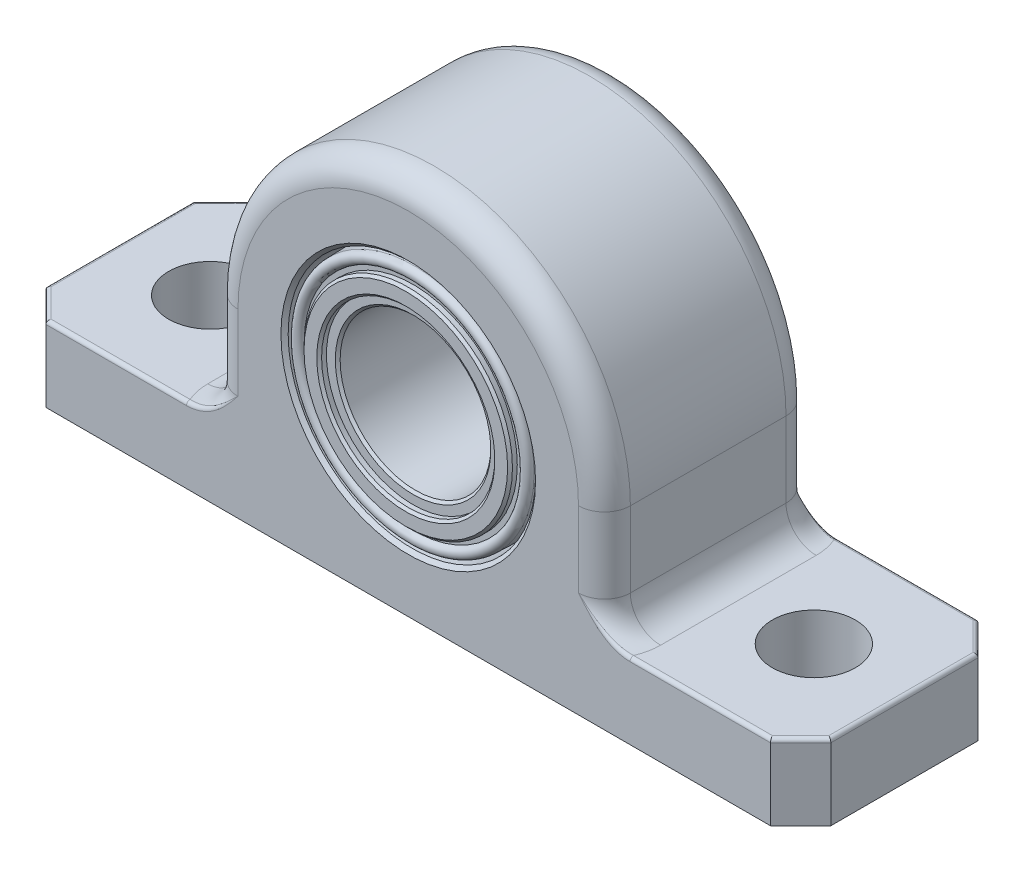
SolidWorks part; units mm, degrees
ref_plane "Front Plane" through (0, 0, 0) normal (0, 0, 1) x (1, 0, 0)
ref_plane "Top Plane" through (0, 0, 0) normal (0, 1, 0) x (1, 0, 0)
ref_plane "Right Plane" through (0, 0, 0) normal (1, 0, 0) x (0, 0, -1)
sketch "Sketch1" plane through (0, 0, 0) normal (0, 0, 1) x (1, 0, 0)
  line L0 (-41.275, 0) -> (41.275, 0)
  line L1 (41.275, 0) -> (41.275, 7.9375)
  line L2 (-41.275, 0) -> (-41.275, 7.9375)
  line L3 (-41.275, 7.9375) -> (-20.6375, 7.9375)
  line L4 (41.275, 7.9375) -> (20.6375, 7.9375)
  line L5 (-20.6375, 7.9375) -> (-20.6375, 19.05)
  line L6 (20.6375, 7.9375) -> (20.6375, 19.05)
  line L7 (0, 0) -> (0, 39.6875) construction
  line L8 (5.6037, 24.6537) -> (14.5929, 33.6429) construction
  circle A0 centre (0, 19.05) radius 7.9248
  arc A1 (20.6375, 19.05) -> (-20.6375, 19.05) centre (0, 19.05) ccw
  circle A2 centre (0, 19.05) radius 13.0099 construction
  point P16 (9.1994, 28.2494)
  point P17 (0, 26.9748)
  point P18 (0, 32.0599)
  dimension "ID" = 15.8496
  dimension "Overall Height" = 39.6875
  dimension "Overall Length" = 82.55
  dimension "CAD B" = 7.9375
  dimension "Center Height" = 19.05
  dimension "D1" = 45
  dimension "D2" = 12.7127
  dimension "D3" = 5.0851
sketch "Sketch2" plane through (0, 0, 0) normal (0, 1, 0) x (1, 0, 0)
  line L0 (-31.75, 0) -> (31.75, 0) construction
  line L1 (-41.275, -10.9141) -> (41.275, 10.9141) construction
  line L2 (-41.275, 10.9141) -> (41.275, 10.9141)
  line L3 (-41.275, 10.9141) -> (-41.275, -10.9141)
  line L4 (-41.275, -10.9141) -> (41.275, -10.9141)
  line L5 (41.275, 10.9141) -> (41.275, -10.9141)
  circle A0 centre (-31.75, 0) radius 4.3656
  circle A1 centre (31.75, 0) radius 4.3656
  dimension "Mounting Hole" = 8.7312
  dimension "Mounting Center" = 63.5
  dimension "Overall Width" = 21.8281
sketch "Sketch3" plane through (0, 0, 0) normal (0, 0, 1) x (1, 0, 0)
  line L0 (-41.275, 0) -> (-41.275, 7.9375) construction
  line L1 (-41.275, 0) -> (41.275, 0) construction
  line L2 (-41.275, 7.9375) -> (-20.6375, 7.9375) construction
  line L3 (41.275, 7.9375) -> (20.6375, 7.9375) construction
  line L4 (41.275, 0) -> (41.275, 7.9375) construction
  line L5 (20.6375, 7.9375) -> (20.6375, 19.05) construction
  line L6 (-20.6375, 7.9375) -> (-20.6375, 19.05) construction
  line L7 (-41.275, 0) -> (-41.275, 7.9375)
  line L8 (-41.275, 0) -> (41.275, 0)
  line L9 (-41.275, 7.9375) -> (-20.6375, 7.9375)
  line L10 (41.275, 7.9375) -> (20.6375, 7.9375)
  line L11 (41.275, 0) -> (41.275, 7.9375)
  line L12 (20.6375, 7.9375) -> (20.6375, 19.05)
  line L13 (-20.6375, 7.9375) -> (-20.6375, 19.05)
  arc A0 (20.6375, 19.05) -> (-20.6375, 19.05) centre (0, 19.05) ccw construction
  circle A1 centre (0, 19.05) radius 13.0099 construction
  arc A2 (20.6375, 19.05) -> (-20.6375, 19.05) centre (0, 19.05) ccw
  circle A3 centre (0, 19.05) radius 13.0099
extrude "Boss-Extrude1" add sketch "Sketch3" against normal up to vertex (10.9141 mm away) and the other way up to vertex (10.9141 mm away) up to point (-41.275, 0, -10.9141) other way up to point (-41.275, 0, 10.9141)
sketch "Sketch4" plane through (0, 0, 0) normal (0, 1, 0) x (1, 0, 0)
  circle A0 centre (-31.75, 0) radius 4.3656 construction
  circle A1 centre (31.75, 0) radius 4.3656 construction
  circle A2 centre (-31.75, 0) radius 4.3656
  circle A3 centre (31.75, 0) radius 4.3656
extrude "Cut-Extrude1" cut sketch "Sketch4" along normal through all
chamfer "Chamfer1" distance 3.175 angle 45 4 edges at (-41.275, 3.9688, -10.9141) (41.275, 3.9688, 10.9141) (41.275, 3.9688, -10.9141) (-41.275, 3.9688, 10.9141)
fillet "Fillet1" radius 2.7285 6 edges at (-20.6375, 13.4938, -10.9141) (0, 39.6875, -10.9141) (-20.6375, 13.4938, 10.9141) (0, 39.6875, 10.9141) (20.6375, 13.4938, -10.9141) (20.6375, 13.4938, 10.9141)
fillet "Fillet2" radius 3.175 6 edges at (-19.8383, 7.9375, -10.1149) (-19.8383, 7.9375, 10.1149) (19.8383, 7.9375, -10.1149) (19.8383, 7.9375, 10.1149) (-20.6375, 7.9375, 0) (20.6375, 7.9375, 0)
chamfer "Chamfer2" distance 0.381 angle 45 2 edges at (13.0099, 19.05, 10.9141) (13.0099, 19.05, -10.9141)
fillet "Fillet3" radius 0.381 14 edges at (-21.6682, 8.1975, -10.9141) (-21.6682, 8.1975, 10.9141) (21.6682, 8.1975, -10.9141) (21.6682, 8.1975, 10.9141) (-30.6221, 7.9375, -10.9141) (-39.6875, 7.9375, -9.3266) (-41.275, 7.9375, 0) (-39.6875, 7.9375, 9.3266) (-30.6221, 7.9375, 10.9141) (30.6221, 7.9375, -10.9141) (39.6875, 7.9375, -9.3266) (41.275, 7.9375, 0) (39.6875, 7.9375, 9.3266) (30.6221, 7.9375, 10.9141)
sketch "Sketch5" plane through (0, 0, 0) normal (1, 0, 0) x (0, 0, -1)
  line L1 (-10.9141, 32.0599) -> (10.9141, 32.0599)
  line L2 (-10.9141, 32.0599) -> (-10.9141, 26.9748)
  line L3 (-10.9141, 26.9748) -> (10.9141, 26.9748)
  line L4 (10.9141, 32.0599) -> (10.9141, 26.9748)
sketch "Sketch6" plane through (0, 0, 0) normal (1, 0, 0) x (0, 0, -1)
  line L0 (0, 32.0599) -> (10.9141, 32.0599)
  line L1 (-10.9141, 32.0599) -> (10.9141, 32.0599) construction
  line L2 (0, 32.0599) -> (-10.3301, 31.6991)
  line L3 (-10.9141, 32.0599) -> (-10.9141, 26.9748) construction
  line L4 (-10.4061, 30.4972) -> (-10.4061, 30.0126)
  line L5 (-10.4061, 30.0126) -> (-11.1681, 30.0126)
  line L6 (-11.1681, 30.0126) -> (-11.1681, 28.1635)
  line L7 (-11.1681, 28.1635) -> (-10.4061, 28.1635)
  line L8 (-10.4061, 28.1635) -> (-10.4061, 26.9748)
  line L9 (-10.9141, 26.9748) -> (10.9141, 26.9748) construction
  line L10 (-10.4061, 26.9748) -> (8.8821, 26.9748)
  line L11 (10.9141, 32.0599) -> (10.9141, 30.4972)
  line L12 (10.9141, 32.0599) -> (10.9141, 26.9748) construction
  line L13 (10.9141, 30.4972) -> (7.1041, 30.4972)
  line L14 (7.1041, 30.4972) -> (7.1041, 30.0126)
  line L15 (7.1041, 30.0126) -> (9.6441, 30.0126)
  line L16 (9.6441, 30.0126) -> (9.6441, 28.1635)
  line L17 (9.6441, 28.1635) -> (8.8821, 28.1635)
  line L18 (8.8821, 28.1635) -> (8.8821, 26.9748)
  line L20 (-10.9141, 19.05) -> (10.9141, 19.05) construction
  line L21 (-10.9141, 0) -> (-10.9141, 7.5565) construction
  arc A0 (-10.3301, 31.6991) -> (-10.4061, 30.4972) centre (-10.309, 31.0944) ccw
  dimension "D1" = 2
  dimension "D2" = 0.254
  dimension "D3" = 0.762
  dimension "D4" = 5.0851
  dimension "D5" = 1.27
  dimension "D6" = 2.54
  dimension "D7" = 1.8491
  dimension "D8" = 1.2019
  dimension "D9" = 18.227
revolve "Revolve1" add sketch "Sketch6" angle 360 about L20
chamfer "Chamfer3" distance 0.254 angle 45 6 edges at (9.1135, 19.05, -9.6441) (10.9626, 19.05, -9.6441) (7.9248, 19.05, 10.4061) (7.9248, 19.05, -8.8821) (10.9626, 19.05, 11.1681) (9.1135, 19.05, 11.1681)
equation "\"D3@Sketch1\"=\"D2@Sketch1\"/2.50"
equation "\"D1@Fillet1\"=\"Overall Width@Sketch2\"/8"
equation "\"D7@Sketch6\"=\"D4@Sketch6\"/2.750"
equation "\"D8@Sketch6\"=\"D7@Sketch6\"*.65"
equation "\"D9@Sketch6\"=\"ID@Sketch1\"*1.15"
